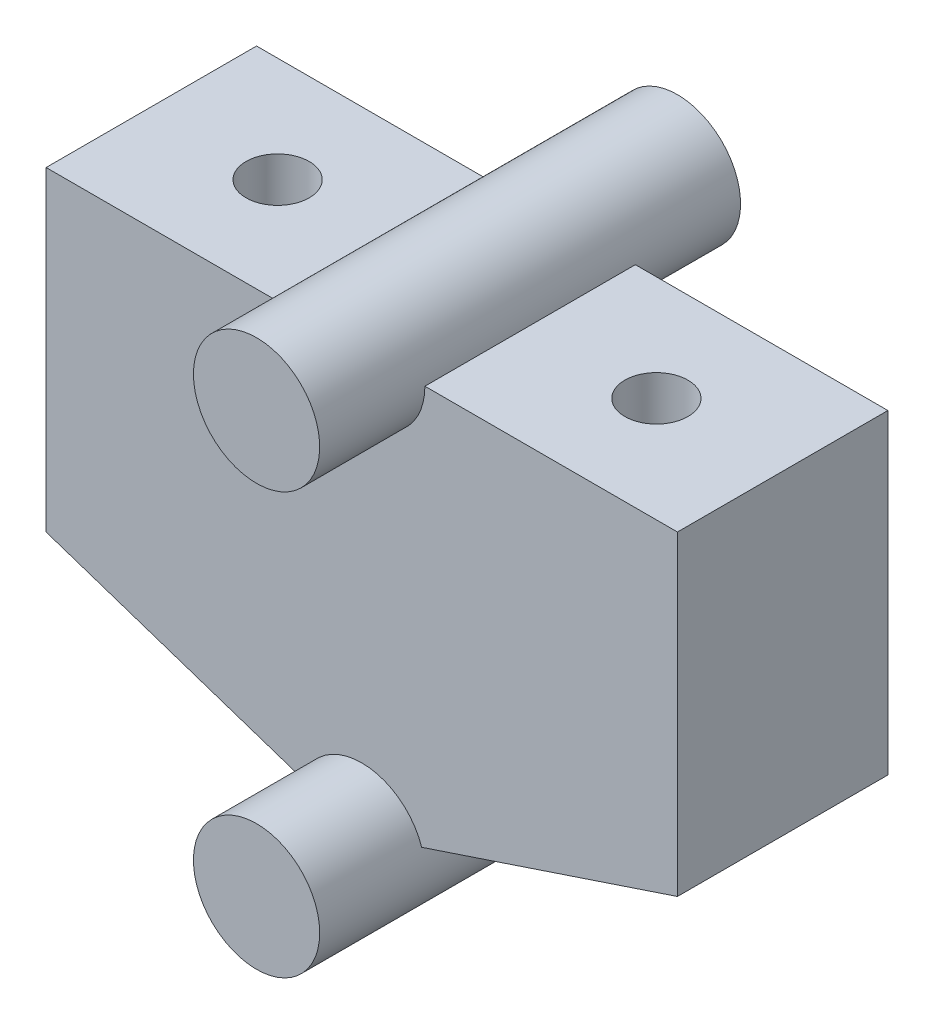
SolidWorks part; units mm, degrees
ref_plane "Front Plane" through (0, 0, 0) normal (0, 0, 1) x (1, 0, 0)
ref_plane "Top Plane" through (0, 0, 0) normal (0, 1, 0) x (1, 0, 0)
ref_plane "Right Plane" through (0, 0, 0) normal (1, 0, 0) x (0, 0, -1)
sketch "Sketch1" plane through (0, 0, 0) normal (0, 0, 1) x (1, 0, 0)
  line L0 (-15, -7.5) -> (-2.846, -11.5513)
  line L1 (-15, 7.5) -> (15, 7.5)
  line L2 (-15, 7.5) -> (-15, -7.5)
  line L4 (15, 7.5) -> (15, -7.5)
  line L5 (-15, 7.5) -> (15, -7.5) construction
  line L6 (-15, -7.5) -> (15, 7.5) construction
  line L7 (2.846, -11.5513) -> (15, -7.5)
  line L8 (-15, -7.5) -> (0, -12.5) construction
  circle A0 centre (0, -12.5) radius 3
  point P0 (0, 0)
  dimension "D4" = 6
  dimension "D1" = 15
  dimension "D2" = 30
  dimension "D3" = 20
extrude "Boss-Extrude1" add sketch "Sketch1" along normal blind 10 contours A0 L7 L4 L1 L2 L0 region at (0, -1.0979, 0)
extrude "Boss-Extrude2" add sketch "Sketch1<3>" along normal blind 15 and the other way blind 5 contours A0 region at (0, -12.5, 0)
sketch "Sketch1<3>" plane through (0, 0, 0) normal (0, 0, 1) x (1, 0, 0) same geometry as "Sketch1"
sketch "Sketch2" plane through (0, 7.5, 0) normal (0, 1, 0) x (1, 0, 0)
  line L0 (-15, 0) -> (15, 0) construction
  line L1 (-15, -10) -> (-15, 0) construction
  line L2 (0, -55) -> (0, 55) construction
  circle A0 centre (-9, -5) radius 1.5
  circle A1 centre (9, -5) radius 1.5
  dimension "D1" = 3
  dimension "D2" = 5
  dimension "D3" = 6
extrude "Cut-Extrude1" cut sketch "Sketch2" against normal through all
sketch "Sketch3" plane through (0, 0, 0) normal (0, 0, -1) x (-1, 0, 0)
  line L0 (15, 7.5) -> (-15, 7.5) construction
  circle A0 centre (0, 7.5) radius 3
  dimension "D1" = 6
extrude "Boss-Extrude3" add sketch "Sketch3" along normal blind 5 and the other way blind 15
